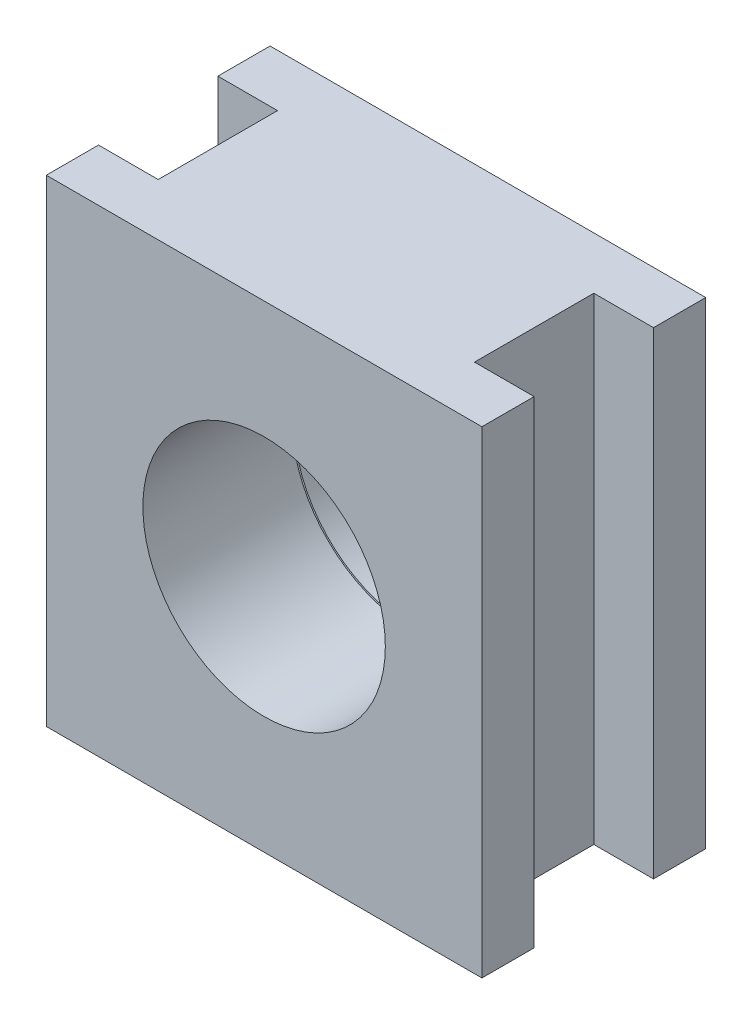
SolidWorks part; units mm, degrees
material "Gray Cast Iron (SN)"
ref_plane "Front Plane" through (0, 0, 0) normal (0, 0, 1) x (1, 0, 0)
ref_plane "Top Plane" through (0, 0, 0) normal (0, 1, 0) x (1, 0, 0)
ref_plane "Right Plane" through (0, 0, 0) normal (1, 0, 0) x (0, 0, -1)
sketch "Sketch1" plane through (0, 0, 0) normal (0, 0, 1) x (1, 0, 0)
  line L1 (13.462, 20.32) -> (-13.462, 20.32)
  line L2 (13.462, 20.32) -> (13.462, -20.32)
  line L3 (13.462, -20.32) -> (-13.462, -20.32)
  line L4 (-13.462, 20.32) -> (-13.462, -20.32)
  line L5 (13.462, 20.32) -> (-13.462, -20.32) construction
  line L6 (13.462, -20.32) -> (-13.462, 20.32) construction
  point P0 (0, 0)
  dimension "D1" = 26.924
  dimension "D2" = 40.64
extrude "Boss-Extrude1" add sketch "Sketch1" along normal blind 19.05
sketch "Sketch2" plane through (13.462, 0, 0) normal (1, 0, 0) x (0, 0, -1)
  line L0 (-19.05, -20.32) -> (0, -20.32) construction
  line L1 (-14.605, -20.32) -> (-4.445, -20.32)
  line L2 (-14.605, -20.32) -> (-14.605, 20.32)
  line L3 (-14.605, 20.32) -> (-4.445, 20.32)
  line L4 (-4.445, -20.32) -> (-4.445, 20.32)
  line L5 (-19.05, 20.32) -> (0, 20.32) construction
  line L6 (-9.525, 20.32) -> (-9.525, -20.32) construction
  line M1 (0, -20.32) -> (0, 20.32)
  line M2 (0, 20.32) -> (-19.05, 20.32)
  line M3 (-19.05, 20.32) -> (-19.05, -20.32)
  line M4 (-19.05, -20.32) -> (0, -20.32)
  dimension "D1" = 10.16
extrude "Boss-Extrude2" add sketch "Sketch2" along normal blind 5.08 contours L2 M4 M2 M3 | L4 M4 M1 M2 region at (13.462, 0, 16.8275) region at (13.462, 0, 2.2225)
mirror "Mirror1" about plane through (0, 0, 0) normal (1, 0, 0) of "Boss-Extrude2"
scale "Scale1" [suppressed]
sketch "Sketch3" plane through (0, 0, 19.05) normal (0, 0, 1) x (1, 0, 0)
  circle A0 centre (0, 0) radius 10.3187
  dimension "D1" = 20.6375
extrude "Cut-Extrude1" cut sketch "Sketch3" against normal blind 12.7
sketch "Sketch4" plane through (0, 0, 6.35) normal (0, 0, 1) x (1, 0, 0)
  circle A0 centre (0, 0) radius 10.16
  dimension "D1" = 20.32
extrude "Cut-Extrude2" cut sketch "Sketch4" against normal blind 3.175
